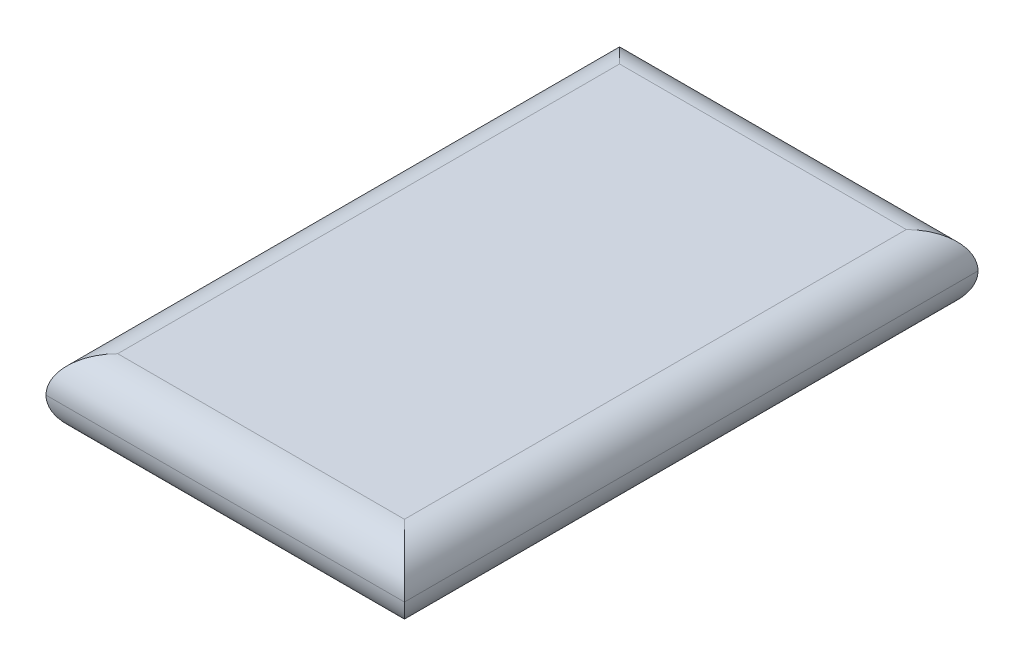
SolidWorks part; units mm, degrees
material "PET"
ref_plane "Front Plane" through (0, 0, 0) normal (0, 0, 1) x (1, 0, 0)
ref_plane "Top Plane" through (0, 0, 0) normal (0, 1, 0) x (1, 0, 0)
ref_plane "Right Plane" through (0, 0, 0) normal (1, 0, 0) x (0, 0, -1)
sketch "Sketch2" plane through (0, 0, 0) normal (1, 0, 0) x (0, 0, -1)
  line L1 (-20.32, 2.54) -> (20.32, 2.54)
  line L2 (-20.32, 2.54) -> (-20.32, -2.54)
  line L3 (-20.32, -2.54) -> (20.32, -2.54)
  line L4 (20.32, 2.54) -> (20.32, -2.54)
  line L5 (-20.32, 2.54) -> (20.32, -2.54) construction
  line L6 (-20.32, -2.54) -> (20.32, 2.54) construction
  point P0 (0, 0)
  dimension "D1" = 40.64
  dimension "D2" = 5.08
extrude "Boss-Extrude1" add sketch "Sketch2" along normal blind 25.4
fillet "Fillet1" radius 2.54 8 edges at (12.7, -2.54, 20.32) (25.4, -2.54, 0) (12.7, -2.54, -20.32) (0, -2.54, 0) (12.7, 2.54, -20.32) (25.4, 2.54, 0) (12.7, 2.54, 20.32) (0, 2.54, 0)
